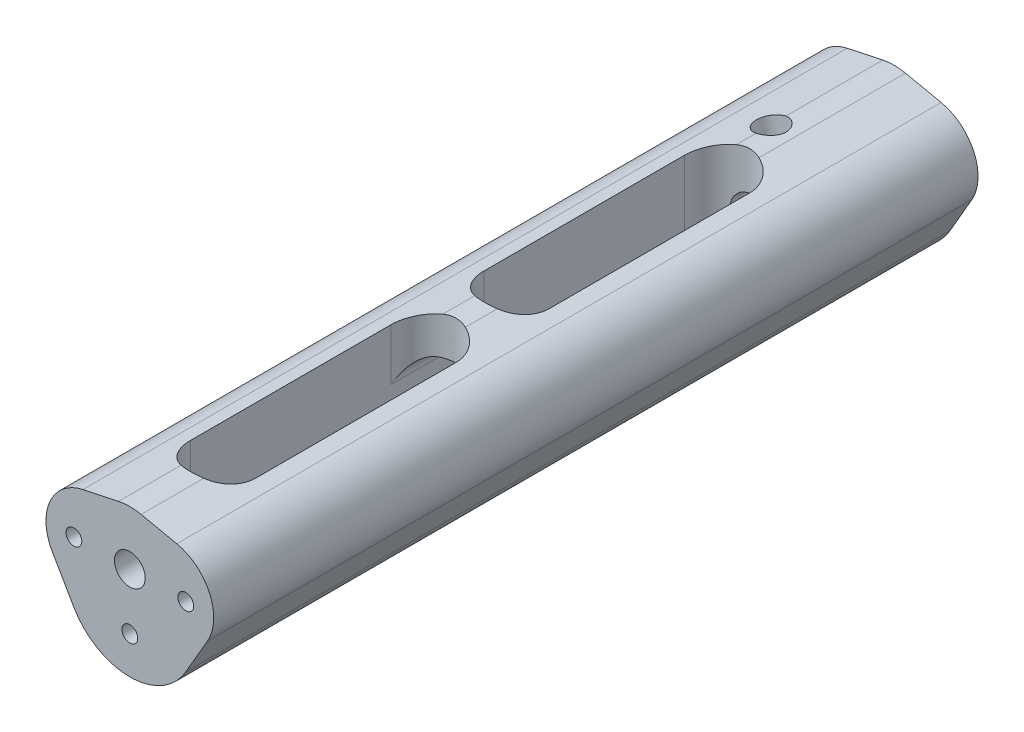
SolidWorks part; units mm, degrees
other "Pillar1"
material "Nylon 101"
ref_plane "Front" through (0, 0, 0) normal (0, 0, 1) x (1, 0, 0)
ref_plane "Top" through (0, 0, 0) normal (0, 1, 0) x (1, 0, 0)
ref_plane "Right" through (0, 0, 0) normal (1, 0, 0) x (0, 0, -1)
ref_axis "Axis" through (0, 0, -80.9) along (0, 0, 1)
sketch "BodySke" plane through (0, 0, 0) normal (0, 0, 1) x (1, 0, 0)
  line L0 (-2, 0) -> (2, 0) construction
  line L1 (-2, 2.5) -> (2, 2.5) construction
  line L2 (-2, -2.5) -> (2, -2.5) construction
  line L3 (4.1651, -1.25) -> (3, -3.2679)
  line L4 (-3, -3.2679) -> (-4.1651, -1.25)
  line L6 (2.5198, 2.4454) -> (0.6062, 2.8521)
  line L7 (-0.6062, 2.8521) -> (-2.5198, 2.4454)
  line L13 (3, 0) -> (-3, 0) construction
  arc A0 (-2, 2.5) -> (-2, -2.5) centre (-2, 0) ccw construction
  arc A1 (2, -2.5) -> (2, 2.5) centre (2, 0) ccw construction
  arc A4 (-3, -3.2679) -> (3, -3.2679) centre (0, -1.5359) ccw
  arc A5 (0.6062, 2.8521) -> (-0.6062, 2.8521) centre (0, 0) ccw
  arc A6 (4.1651, -1.25) -> (2.5198, 2.4454) centre (2, 0) ccw
  arc A7 (-4.1651, -1.25) -> (-2.5198, 2.4454) centre (-2, 0) cw
  circle A9 centre (0, 0) radius 0.825
  circle A15 centre (-3, 0) radius 0.425
  circle A16 centre (3, 0) radius 0.425
  circle A17 centre (0, -3) radius 0.425
  point P2 (0, 0)
  point P19 (0, -5)
  point P44 (0, 0)
  dimension "D3" = 1.65
  dimension "D6" = 3
  dimension "D4" = 0.85
  dimension "D5" = 12
  dimension "D1" = 4
  dimension "D2" = 5
  dimension "D7" = 5
  dimension "D8" = 6
  dimension "D10" = 6
extrude "Body" add sketch "BodySke" along normal blind 41
ref_plane "Plane" through (0, 0, 0) normal (-0.9781, -0.2079, 0) x (0, 0, 1)
sketch "HoleSke" plane through (0, 0, 0) normal (-0.9781, -0.2079, 0) x (0, 0, 1)
  line L1 (6, 2.9158) -> (6, 1.7045)
  line L2 (41, 2.9158) -> (0, 2.9158) construction
  line L3 (0, 2.9158) -> (0, -0.3567) construction
  spline S0 degree 3 poles (0, 0) (4.6199, 0) (6, 0.036) (6, 1.7045) knots 0 0 0 0 1 1 1 1
  dimension "D1" = 6
sweep "Hole" cut path "HoleSke" circular profile diameter 1.6 parameters "D3"=1.6
sketch "Cut1Ske" plane through (0, 0, 0) normal (0, 1, 0) x (1, 0, 0)
  line L0 (0, -9.5) -> (0, -36) construction
  line L1 (1.75, -9.5) -> (1.75, -36)
  line L2 (-1.75, -9.5) -> (-1.75, -36)
  line L3 (-3, -41) -> (3, -41) construction
  line L4 (3, 0) -> (-3, 0) construction
  arc A0 (1.75, -9.5) -> (-1.75, -9.5) centre (0, -9.5) ccw
  arc A1 (-1.75, -36) -> (1.75, -36) centre (0, -36) ccw
  point P2 (0, -22.75)
  dimension "D1" = 5
  dimension "D2" = 9.5
  dimension "D3" = 3.5
extrude "Cut1" cut sketch "Cut1Ske" against normal through all and the other way blind 0.825
sketch "Cut2Ske" plane through (0, 0, 0) normal (0, 1, 0) x (1, 0, 0)
  line L0 (0, -20.25) -> (0, -9.5) construction
  line L1 (0, -9.5) -> (0, -36) construction
  line L2 (-1.75, -20.25) -> (-1.75, -9.5)
  line L3 (1.75, -20.25) -> (1.75, -9.5)
  line L4 (1.75, -9.5) -> (1.75, -36) construction
  line L5 (0, -25.25) -> (0, -36) construction
  line L6 (1.75, -25.25) -> (1.75, -36)
  line L7 (-1.75, -25.25) -> (-1.75, -36)
  line L8 (0, -20.25) -> (0, -25.25) construction
  arc A0 (-1.75, -20.25) -> (1.75, -20.25) centre (0, -20.25) ccw
  arc A1 (1.75, -9.5) -> (-1.75, -9.5) centre (0, -9.5) ccw
  arc A2 (1.75, -25.25) -> (-1.75, -25.25) centre (0, -25.25) ccw
  arc A3 (-1.75, -36) -> (1.75, -36) centre (0, -36) ccw
  point P5 (0, -14.875)
  point P13 (0, -30.625)
  point P20 (0, -22.75)
  dimension "D1" = 5
extrude "Cut2" cut sketch "Cut2Ske" along normal through all
fillet "Fillet" radius 1 2 edges at (-1.75, 0.825, 22.75) (1.75, 0.825, 22.75)
